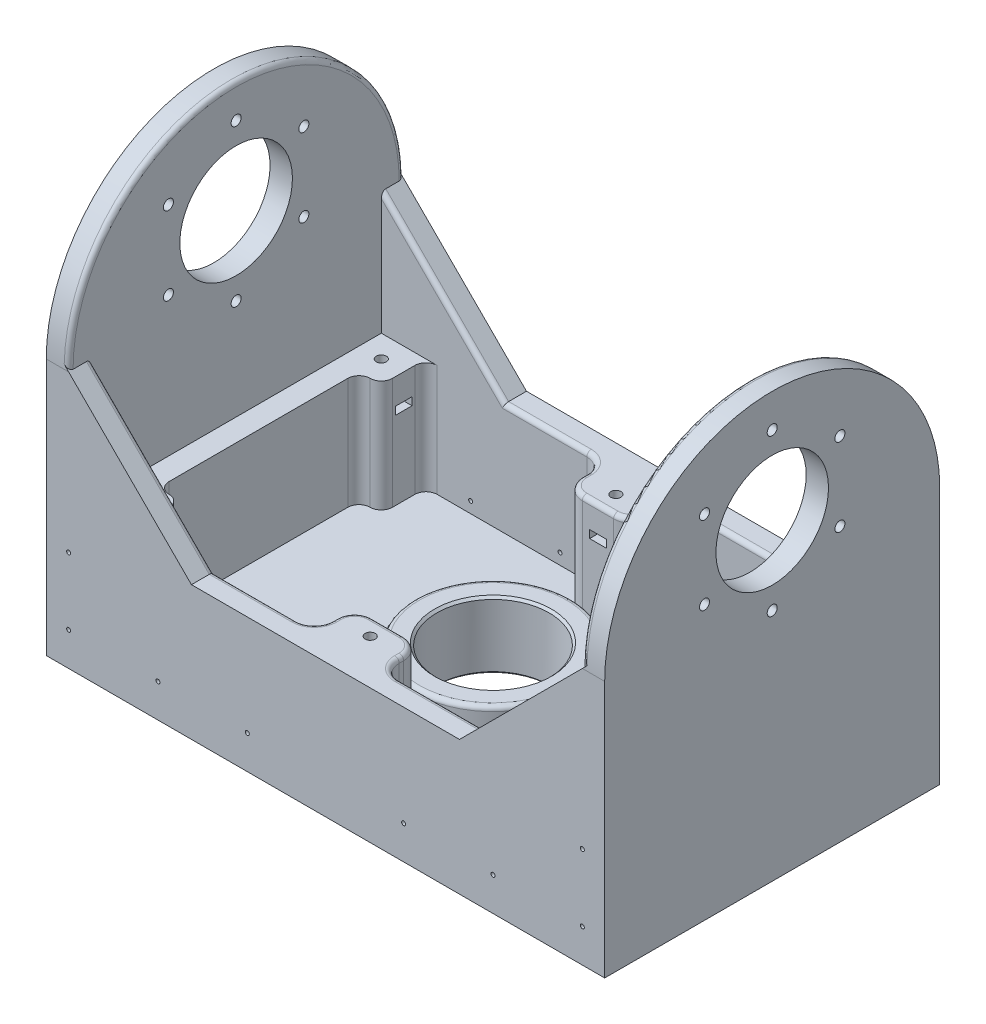
SolidWorks part; units mm, degrees
note: '?' marks a value the reader was unsure of.
ref_plane "Front Plane" through (0, 0, 0) normal (0, 0, 1) x (1, 0, 0)
ref_plane "Top Plane" through (0, 0, 0) normal (0, 1, 0) x (1, 0, 0)
ref_plane "Right Plane" through (0, 0, 0) normal (1, 0, 0) x (0, 0, -1)
sketch "Sketch3" plane through (0, 0, 0) normal (0, 1, 0) x (1, 0, 0)
  line L0 (0, -93.3232) -> (0, 91.047) construction
  line L1 (-147.1927, 0) -> (149.8483, 0) construction
  line L3 (-125, -75) -> (125, -75)
  line L4 (-125, -75) -> (-125, 75)
  line L5 (-125, 75) -> (125, 75)
  line L6 (125, -75) -> (125, 75)
  line L7 (-125, -75) -> (125, 75) construction
  line L8 (-125, 75) -> (125, -75) construction
  point P5 (0, 0)
  dimension "D1" = 250
  dimension "D2" = 150
extrude "Boss-Extrude1" add sketch "Sketch3" along normal blind 10
ref_axis "Axis1" through (0, 0, 0) along (0, 1, 0)?
sketch "Sketch4" plane through (0, 10, 0) normal (0, 1, 0) x (1, 0, 0)
  circle A0 centre (0, 0) radius 35
  dimension "D1" = 70
extrude "Boss-Extrude2" add sketch "Sketch4" along normal blind 20
sketch "Sketch5" plane through (0, 30, 0) normal (0, 1, 0) x (1, 0, 0)
  circle A0 centre (0, 0) radius 25.15
  dimension "D1" = 50.3
extrude "Cut-Extrude1" cut sketch "Sketch5" against normal through all
chamfer "Chamfer1" distance 1 angle 45 2 edges at (0, 0, 25.15) (0, 30, 25.15)
fillet "Fillet1" radius 2 1 edges at (0, 30, 35)
fillet "Fillet2" radius 10 1 edges at (0, 10, 35)
sketch "Sketch8" plane through (-125, 0, 0) normal (-1, 0, 0) x (0, 0, 1)
  line L0 (-75, 10) -> (-75, 115)
  line L1 (0, 0) -> (0, 254.622) construction
  line L2 (0, 0) -> (0, 96.2107) construction
  line L4 (75, 10) -> (75, 115)
  line L5 (-75, 10) -> (75, 10)
  arc A0 (-75, 115) -> (75, 115) centre (0, 115) cw
  dimension "D2" = 75
extrude "Boss-Extrude3" add sketch "Sketch8" against normal blind 10
mirror "Mirror1" about plane through (0, 0, 0) normal (1, 0, 0) of "Boss-Extrude3"
sketch "Sketch9" plane through (0, 10, 0) normal (0, 1, 0) x (1, 0, 0)
  line L0 (-115, -75) -> (115, -75) construction
  line L1 (115, 75) -> (115, -75) construction
  line L2 (115, 75) -> (-115, 75) construction
  line L3 (-115, -75) -> (-115, 75) construction
  line L4 (-115, -75) -> (115, -75)
  line L5 (115, 75) -> (115, -75)
  line L6 (115, 75) -> (-115, 75)
  line L7 (-115, -75) -> (-115, 75)
  line L8 (105, 65) -> (-105, 65)
  line L9 (-105, -65) -> (-105, 65)
  line L10 (-105, -65) -> (105, -65)
  line L11 (105, 65) -> (105, -65)
  dimension "D1" = 10
extrude "Boss-Extrude4" add sketch "Sketch9" along normal blind 50
sketch "Sketch10" plane through (0, 0, 75) normal (0, 0, 1) x (1, 0, 0)
  line L0 (-115, 115) -> (-60, 60)
  line L1 (-115, 60) -> (115, 60) construction
  line L2 (-60, 60) -> (-115, 60)
  line L3 (-115, 60) -> (-115, 115)
extrude "Boss-Extrude5" add sketch "Sketch10" against normal blind 10
sketch "Sketch11" plane through (0, 10, 0) normal (0, 1, 0) x (1, 0, 0)
  line L0 (-115, -75) -> (-115, 75) construction
  line L6 (-60, -65) -> (-115, -65) construction
  line L7 (-105, -65) -> (-95, -65)
  line L8 (-105, -65) -> (-105, -45)
  line L9 (-105, -45) -> (-95, -45)
  line L10 (-95, -65) -> (-95, -45)
  dimension "D3" = 20
  dimension "D4" = 20
extrude "Boss-Extrude7" add sketch "Sketch11" along normal up to surface (50 mm away) up to face at (-12, 60, 13)
sketch "Sketch13" plane through (0, 60, 0) normal (0, 1, 0) x (1, 0, 0)
  circle A0 centre (-105, -55) radius 2.25
  dimension "D1" = 4.5
extrude "Cut-Extrude2" cut sketch "Sketch13" against normal blind 25
ref_plane "Plane2" through (0, 45, 0) normal (0, 1, 0) x (1, 0, 0)
sketch "Sketch14" plane through (0, 45, 0) normal (0, 1, 0) x (1, 0, 0)
  line L0 (-105, -55) -> (-95, -55) construction
  line L1 (-95, -65) -> (-95, -45) construction
  line L2 (-102.8349, -51.25) -> (-95, -51.25)
  line L4 (-102.8349, -51.25) -> (-107.1651, -51.25)
  line L5 (-107.1651, -51.25) -> (-109.3301, -55)
  line L6 (-109.3301, -55) -> (-107.1651, -58.75)
  line L7 (-107.1651, -58.75) -> (-102.8349, -58.75)
  line L9 (-95, -51.25) -> (-95, -58.75)
  line L10 (-95, -65) -> (-95, -45) construction
  line L11 (-95, -58.75) -> (-102.8349, -58.75)
  line L13 (-101.7524, -53.125) -> (-102.8349, -51.25) [skipped]
  line L14 (-102.8349, -58.75) -> (-101.7524, -56.875) [skipped]
  circle A0 centre (-105, -55) radius 3.75 construction
  dimension "D1" = 7.5
extrude "Cut-Extrude3" cut sketch "Sketch14" along normal blind 3.5
fillet "Fillet3" radius 5 3 edges at (-95, 35, 65) (-105, 35, 45) (-95, 35, 45)
mirror "Mirror2" about plane through (0, 0, 0) normal (0, 0, 1) of "Cut-Extrude3", "Cut-Extrude2", "Boss-Extrude7", "Boss-Extrude5"
mirror "Mirror3" about plane through (0, 0, 0) normal (1, 0, 0) of "Mirror2", "Boss-Extrude5", "Boss-Extrude7", "Cut-Extrude2", "Cut-Extrude3"
fillet "Fillet4" radius 5 15 edges at (-100, 10, -45) (-95, 35, -65) (-95, 35, -45) (-100, 60, -45) (-105, 35, -45) (105, 35, -45) (95, 35, -65) (95, 35, -45) (100, 10, -45) (100, 60, -45) (100, 10, 45) (95, 35, 65) (95, 35, 45) (100, 60, 45) (105, 35, 45)
sketch "Sketch15" plane through (0, 10, 0) normal (0, 1, 0) x (1, 0, 0)
  line L0 (0, 65) -> (0, -65) construction
  line L1 (60, 65) -> (-60, 65) construction
  line L2 (-60, -65) -> (60, -65) construction
  line L3 (-15, -65) -> (-15, -47)
  line L4 (-15, -47) -> (15, -47)
  line L5 (15, -65) -> (15, -47)
  line L6 (-15, -65) -> (15, -65)
  point P10 (0, -47)
  dimension "D1" = 30
  dimension "D2" = 18
extrude "Boss-Extrude8" add sketch "Sketch15" along normal up to surface (50 mm away) up to face at (0, 60, 70)
sketch "Sketch17" plane through (0, 60, 0) normal (0, 1, 0) x (1, 0, 0)
  line L0 (-105, -55) -> (105, -55) construction
  circle A0 centre (0, -55) radius 2.25
  dimension "D1" = 4.5
extrude "Cut-Extrude4" cut sketch "Sketch17" against normal blind 25
sketch "Sketch18" plane through (0, 45, 0) normal (0, 1, 0) x (1, 0, 0)
  line L0 (-3.75, -52.8349) -> (-3.75, -47)
  line L1 (0, -59.3301) -> (3.75, -57.1651)
  line L2 (3.75, -57.1651) -> (3.75, -52.8349)
  line L5 (-3.75, -52.8349) -> (-3.75, -57.1651)
  line L6 (-3.75, -57.1651) -> (0, -59.3301)
  line L7 (15, -47) -> (-15, -47) construction
  line L8 (3.75, -52.8349) -> (3.75, -47)
  line L9 (-3.75, -47) -> (3.75, -47)
  line L10 (0, -50.6699) -> (-1.875, -51.7524) [skipped]
  line L11 (3.75, -52.8349) -> (1.875, -51.7524) [skipped]
  circle A0 centre (0, -55) radius 3.75 construction
  dimension "D1" = 7.5
extrude "Cut-Extrude5" cut sketch "Sketch18" along normal blind 3.5
fillet "Fillet5" radius 8 4 edges at (-15, 35, 65) (15, 35, 65) (15, 35, 47) (-15, 35, 47)
mirror "Mirror4" about plane through (0, 0, 0) normal (0, 0, 1) of "Cut-Extrude4", "Boss-Extrude8", "Cut-Extrude5"
fillet "Fillet6" radius 8 4 edges at (15, 35, -47) (-15, 35, -47) (-15, 35, -65) (15, 35, -65)
sketch "Sketch19" plane through (125, 0, 0) normal (1, 0, 0) x (0, 0, -1)
  line L0 (0, 190) -> (0, 103.1193) construction
  line L1 (-75, 0) -> (75, 0) construction
  arc A0 (75, 115) -> (-75, 115) centre (0, 115) ccw construction
  circle A1 centre (0, 140) radius 25.2
  dimension "D2" = 50.4
  dimension "D1" = 140
extrude "Cut-Extrude6" cut sketch "Sketch19" against normal up to next
sketch "Sketch20" plane through (125, 0, 0) normal (1, 0, 0) x (0, 0, -1)
  line L0 (0, 140) -> (0, 100.9701) construction
  circle A0 centre (0, 105) radius 2.25
  dimension "D1" = 4.5
  dimension "D2" = 35
extrude "Cut-Extrude7" cut sketch "Sketch20" against normal up to next
pattern_circular "CirPattern1" count 6 over 360 about axis through (0, 140, 0) along (1, 0, 0) of "Cut-Extrude7"
mirror "Mirror5" about plane through (0, 0, 0) normal (1, 0, 0) of "Cut-Extrude6", "CirPattern1", "Cut-Extrude7"
sketch "Sketch21" plane through (115, 0, 0) normal (-1, 0, 0) x (0, 0, 1)
  line L1 (0, 170.6699) -> (3.75, 172.8349)
  line L2 (3.75, 172.8349) -> (3.75, 177.1651)
  line L3 (3.75, 177.1651) -> (0, 179.3301)
  line L4 (0, 179.3301) -> (-3.75, 177.1651)
  line L5 (-3.75, 177.1651) -> (-3.75, 172.8349)
  line L6 (-3.75, 172.8349) -> (0, 170.6699)
  circle A0 centre (0, 175) radius 3.75 construction
  dimension "D1" = 7.5
extrude "Cut-Extrude8" cut sketch "Sketch21" against normal blind 3.5
pattern_circular "CirPattern2" count 6 over 360 about axis through (0, 140, 0) along (1, 0, 0) of "Cut-Extrude8"
fillet "Fillet7" radius 2 24 edges at (-41.5, 60, 65) (-87.5, 87.5, 65) (-87.5, 87.5, -65) (41.5, 60, -65) (87.5, 87.5, -65) (87.5, 87.5, 65) (-15, 60, 56) (15, 60, 56) (41.5, 60, 65) (0, 60, 47) (-12.6569, 60, 49.3431) (12.6569, 60, 49.3431) (-17.3431, 60, 62.6569) (17.3431, 60, 62.6569) (15, 60, -56) (0, 60, -47) (-115, 190, 0) (-41.5, 60, -65) (-15, 60, -56) (-12.6569, 60, -49.3431) (12.6569, 60, -49.3431) (17.3431, 60, -62.6569) (-17.3431, 60, -62.6569) (115, 190, 0)
sketch "Sketch22" plane through (0, 0, 75) normal (0, 0, 1) x (1, 0, 0)
  line L0 (-125, 15) -> (125, 15) construction
  line L1 (-125, 115) -> (-125, 0) construction
  line L2 (125, 115) -> (125, 0) construction
  line L3 (0, 0) -> (0, 60) construction
  line L4 (-60, 60) -> (60, 60) construction
  line L5 (-115, 0) -> (-115, 84.4381) construction
  line L6 (-125, 0) -> (125, 0) construction
  circle A0 centre (-115, 15) radius 0.9
  circle A1 centre (-115, 45) radius 0.9
  circle A2 centre (-75, 15) radius 0.9
  circle A3 centre (-35, 15) radius 0.9
  dimension "D3" = 1.8
  dimension "D4" = 1.8
  dimension "D5" = 1.8
  dimension "D6" = 1.8
  dimension "D1" = 10
  dimension "D2" = 15
  dimension "D7" = 30
  dimension "D8" = 40
  dimension "D9" = 40
extrude "Cut-Extrude10" cut sketch "Sketch22" against normal blind 10
mirror "Mirror6" about plane through (0, 0, 0) normal (1, 0, 0) of "Cut-Extrude10"
mirror "Mirror7" about plane through (0, 0, 0) normal (0, 0, 1) of "Mirror6", "Cut-Extrude10"
